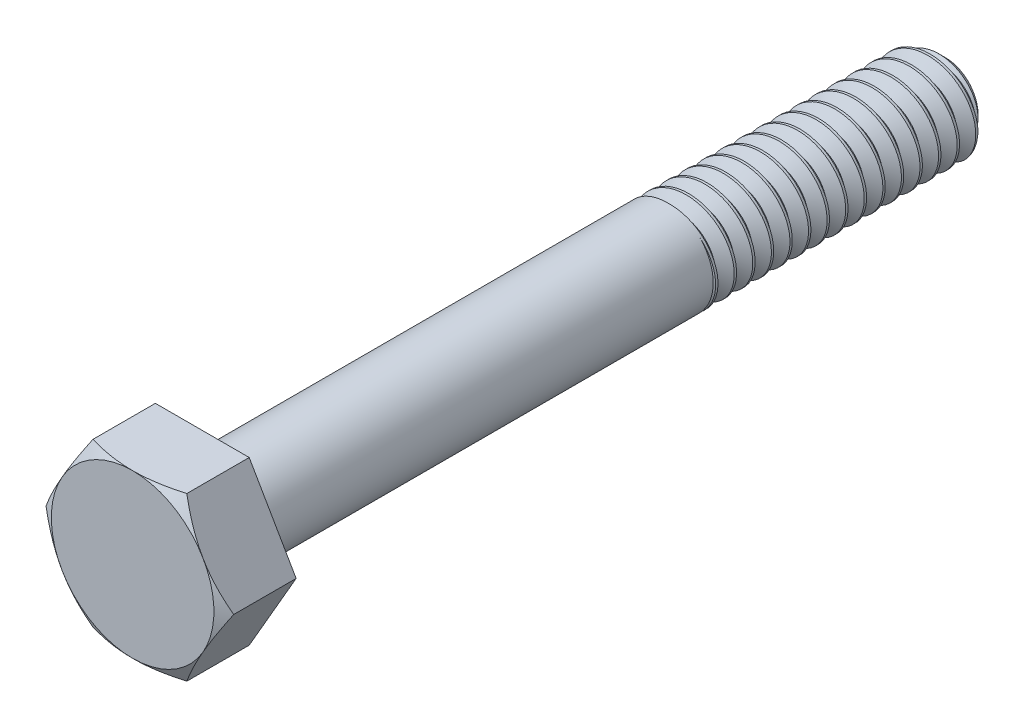
SolidWorks part; units mm, degrees
ref_plane "Front Plane" through (0, 0, 0) normal (0, 0, 1) x (1, 0, 0)
ref_plane "Top Plane" through (0, 0, 0) normal (0, 1, 0) x (1, 0, 0)
ref_plane "Right Plane" through (0, 0, 0) normal (1, 0, 0) x (0, 0, -1)
sketch "Sketch1" plane through (0, 0, 0) normal (1, 0, 0) x (0, 0, -1)
  line L0 (-27.7812, 0) -> (-27.7812, 5.5562)
  line L1 (-27.7812, 5.5562) -> (-23.0187, 5.5562)
  line L2 (-23.0187, 5.5562) -> (-23.0187, 3.175)
  line L3 (-23.0187, 3.175) -> (26.8288, 3.175)
  line L4 (26.8288, 3.175) -> (27.7812, 2.2225)
  line L5 (27.7812, 2.2225) -> (27.7812, 0)
  line L6 (27.7812, 0) -> (-27.7812, 0) construction
  line L7 (27.7019, 3.3125) -> (28.3369, 2.2126) construction
  line L8 (28.3369, 2.2126) -> (28.9719, 3.3125) construction
  line L9 (28.9719, 3.3125) -> (27.7019, 3.3125) construction
  line L10 (28.3369, 2.2126) -> (28.3369, 2.3501) construction
  line L11 (28.2575, 2.3501) -> (28.4162, 2.3501) construction
  line L12 (27.7812, 3.175) -> (28.8925, 3.175) construction
  line L13 (28.3369, 3.3125) -> (28.3369, 3.175) construction
  line L14 (28.9322, 3.2437) -> (27.7416, 3.2437)
  line L15 (27.7416, 3.2437) -> (28.2575, 2.3501)
  line L16 (28.2575, 2.3501) -> (28.4162, 2.3501)
  line L17 (28.4162, 2.3501) -> (28.9322, 3.2437)
  line L18 (27.7812, -3.175) -> (24.6062, -3.175) construction
  point P2 (8.7312, 3.175)
  point P8 (-23.0187, 4.3656)
  point P22 (28.3369, 3.2437)
  point P23 (27.7812, -3.175)
  point P27 (27.7812, 3.175)
  dimension "Length" = 50.8
  dimension "Head Height" = 4.7625
  dimension "Theard size" = 6.35
  dimension "Head Width" = 11.1125
  dimension "Pitch" = 1.27
  dimension "D1" = 0.1588
  dimension "D2" = 45
  dimension "D3" = 0.9525
  dimension "D4" = 3.175
  dimension "Thread Length" = 19.05
sketch "Sketch2" plane through (0, 0, 0) normal (0, 0, 1) x (1, 0, 0)
  line L1 (-3.2079, 5.5562) -> (-6.4158, 0)
  line L2 (-6.4158, 0) -> (-3.2079, -5.5562)
  line L3 (-3.2079, -5.5562) -> (3.2079, -5.5562)
  line L4 (3.2079, -5.5562) -> (6.4158, 0)
  line L5 (6.4158, 0) -> (3.2079, 5.5562)
  line L6 (3.2079, 5.5562) -> (-3.2079, 5.5562)
  circle A0 centre (0, 0) radius 5.5562 construction
  dimension "D1" = 11.1125
sketch "Sketch3" plane through (0, 0, 0) normal (1, 0, 0) x (0, 0, -1)
  line L0 (-27.7812, 0) -> (-27.7812, 5.5562) construction
  line L1 (-27.7812, 5.5562) -> (-23.0187, 5.5562) construction
  line L2 (-23.0187, 5.5562) -> (-23.0187, 3.175) construction
  line L3 (-23.0187, 3.175) -> (26.8288, 3.175) construction
  line L4 (26.8288, 3.175) -> (27.7812, 2.2225) construction
  line L5 (27.7812, 2.2225) -> (27.7812, 0) construction
  line L6 (-27.7812, 0) -> (-27.7812, 5.5562)
  line L7 (-27.7812, 5.5562) -> (-23.0187, 5.5562)
  line L8 (-23.0187, 5.5562) -> (-23.0187, 3.175)
  line L9 (-23.0187, 3.175) -> (26.8288, 3.175)
  line L10 (26.8288, 3.175) -> (27.7812, 2.2225)
  line L11 (27.7812, 2.2225) -> (27.7812, 0)
  line L12 (27.7812, 0) -> (-27.7812, 0) construction
  line L13 (27.7812, 0) -> (-27.7812, 0)
revolve "Revolve1" add sketch "Sketch3" angle 360 about L6
sketch "Sketch4" plane through (0, 0, 27.7812) normal (0, 0, 1) x (1, 0, 0)
  line L0 (6.4158, 0) -> (3.2079, 5.5562) construction
  line L1 (3.2079, 5.5562) -> (-3.2079, 5.5562) construction
  line L2 (-3.2079, 5.5562) -> (-6.4158, 0) construction
  line L3 (-6.4158, 0) -> (-3.2079, -5.5562) construction
  line L4 (-3.2079, -5.5562) -> (3.2079, -5.5562) construction
  line L5 (3.2079, -5.5562) -> (6.4158, 0) construction
  line L6 (6.4158, 0) -> (3.2079, 5.5562)
  line L7 (3.2079, 5.5562) -> (-3.2079, 5.5562)
  line L8 (-3.2079, 5.5562) -> (-6.4158, 0)
  line L9 (-6.4158, 0) -> (-3.2079, -5.5562)
  line L10 (-3.2079, -5.5562) -> (3.2079, -5.5562)
  line L11 (3.2079, -5.5562) -> (6.4158, 0)
extrude "Boss-Extrude1" add sketch "Sketch4" against normal up to surface (4.7625 mm away) up to face at (-5.5562, 0, 23.0187)
sketch "Sketch5" plane through (0, 0, 27.7812) normal (0, 0, 1) x (1, 0, 0)
  circle A0 centre (0, 0) radius 5.5562 construction
  circle A1 centre (0, 0) radius 5.5562
extrude "Cut-Extrude1" cut sketch "Sketch5" against normal through all draft 60 flip side to cut
chamfer "Chamfer1" distance 0.127 angle 45 1 edges at (-3.175, 0, 23.0187)
ref_plane "Plane1" through (0, 0, -8.7312) normal (0, 0, 1) x (1, 0, 0)
split "Split1" trim tools "Plane1" bodies to split 106 resulting bodies 107 108
sketch "Sketch6" plane through (0, 0, -27.7812) normal (0, 0, -1) x (-1, 0, 0)
  circle A0 centre (0, 0) radius 3.175 construction
  circle A1 centre (0, 0) radius 3.175
curve "Helix/Spiral1" pitch 1.27 height 21.59 radius 3.175 centre (0, 0, -27.7812) axis (0, 0, 1) start towards (0, 1, 0)
sketch "Sketch7" plane through (0, 0, 0) normal (1, 0, 0) x (0, 0, -1)
  line L0 (27.7416, 3.2437) -> (28.2575, 2.3501) construction
  line L1 (28.2575, 2.3501) -> (28.4162, 2.3501) construction
  line L2 (28.4162, 2.3501) -> (28.9322, 3.2437) construction
  line L3 (28.9322, 3.2437) -> (27.7416, 3.2437) construction
  line L4 (27.7416, 3.2437) -> (28.2575, 2.3501)
  line L5 (28.2575, 2.3501) -> (28.4162, 2.3501)
  line L6 (28.4162, 2.3501) -> (28.9322, 3.2437)
  line L7 (28.9322, 3.2437) -> (27.7416, 3.2437)
sweep "Cut-Sweep2" cut profiles "Sketch7" path "Helix/Spiral1" align with end faces yes
sketch "Sketch8" plane through (0, 0, -8.7312) normal (0, 0, -1) x (-1, 0, 0)
  circle A0 centre (0, 0) radius 3.175 construction
  circle A1 centre (0, 0) radius 3.175
extrude "Boss-Extrude2" add sketch "Sketch8" along normal through all draft 60
equation "\"D1@Sketch1\"=\"Pitch@Sketch1\"/8"
equation "\"D3@Sketch1\"=\"Pitch@Sketch1\"*.75"
equation "\"D4@Sketch1\"=\"Pitch@Sketch1\"*2.5"
equation "\"D4@Helix/Spiral1\"=\"Pitch@Sketch1\""
equation "\"D3@Helix/Spiral1\"=\"Thread Length@Sketch1\"+\"Pitch@Sketch1\"*2"
equation "\"D1@Chamfer1\"=\"Theard size@Sketch1\"*.02"
